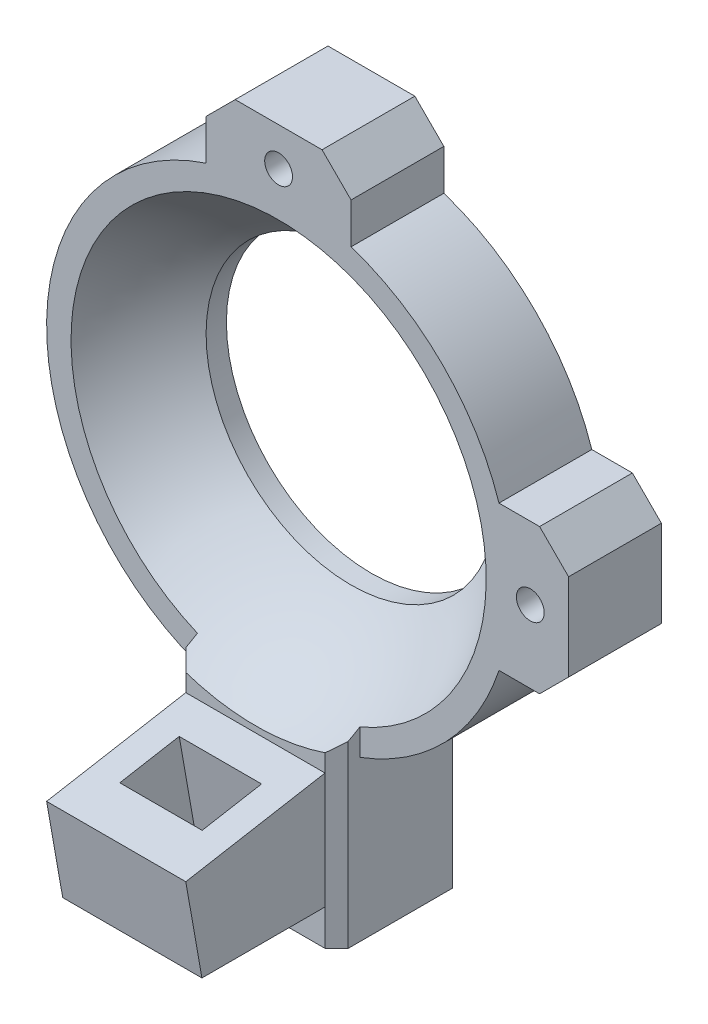
SolidWorks part; units mm, degrees
material "ABS"
ref_plane "Front Plane" through (0, 0, 0) normal (0, 0, 1) x (1, 0, 0)
ref_plane "Top Plane" through (0, 0, 0) normal (0, 1, 0) x (1, 0, 0)
ref_plane "Right Plane" through (0, 0, 0) normal (1, 0, 0) x (0, 0, -1)
sketch "Sketch1" plane through (0, 0, 0) normal (0, 0, 1) x (1, 0, 0)
  line L1 (-6.245, 21) -> (6.245, 21)
  line L2 (-6.245, 21) -> (-6.245, 19)
  line L3 (21, 6.245) -> (19, 6.245)
  line L4 (6.245, 21) -> (6.245, 19)
  line L5 (-6.245, 21) -> (6.245, 19) construction
  line L6 (-6.245, 19) -> (6.245, 21) construction
  line L7 (21, 6.245) -> (21, -6.245)
  line L8 (21, -6.245) -> (19, -6.245)
  line L10 (21, 6.245) -> (19, -6.245) construction
  line L11 (21, -6.245) -> (19, 6.245) construction
  circle A0 centre (0, 0) radius 12.5
  arc A1 (-6.245, 19) -> (0, -20) centre (0, 0) ccw
  arc A2 (19, 6.245) -> (6.245, 19) centre (0, 0) ccw
  arc A3 (0, -20) -> (19, -6.245) centre (0, 0) ccw
  point P3 (20, 0)
  point P4 (0, 20)
  point P13 (0, -20)
  dimension "D1" = 40
  dimension "D2" = 25
  dimension "D3" = 1
  dimension "D4" = 1
extrude "Boss-Extrude1" add sketch "Sketch1" along normal blind 8
ref_axis "Axis1" through (0, 0, 8) along (0, 0, -1)
sketch "Sketch18" plane through (0, 0, 0) normal (0, 0, 1) x (1, 0, 0)
  line L0 (-17, -10.5357) -> (-17, -19.7737)
  line L1 (-17, -19.7737) -> (-3, -19.7737)
  arc A0 (-6.245, 19) -> (19, -6.245) centre (0, 0) ccw construction
  arc A3 (-17, -10.5357) -> (-3, -19.7737) centre (0, 0) ccw
  point P5 (-10, -19.7737)
  dimension "D1" = 14
  dimension "D2" = 10
extrude "Boss-Extrude7" [suppressed] add sketch "Sketch18" along normal up to surface (8 mm away)
sketch "Sketch3" plane through (0, 0, 0) normal (0, 0, 1) x (1, 0, 0)
  line L0 (0, 0) -> (0, -32.5) construction
  line L1 (-7, -18.735) -> (-7, -32.5)
  line L2 (-7, -32.5) -> (7, -32.5)
  line L3 (7, -18.735) -> (7, -32.5)
  line L4 (-7, -18.735) -> (-7, -15.235)
  line L5 (-7, -15.235) -> (7, -15.235)
  line L6 (7, -15.235) -> (7, -18.735)
  circle A0 centre (0, 0) radius 20 construction
  dimension "D1" = 32.5
  dimension "D2" = 14
  dimension "D3" = 3.5
extrude "Boss-Extrude2" add sketch "Sketch3" along normal blind 10
sketch "Sketch2" plane through (0, 0, 0) normal (0, 1, 0) x (1, 0, 0)
  line L0 (0, -8) -> (0, 0) construction
  line L1 (0, -38.5) -> (0, 2.5)
  arc A0 (0, 2.5) -> (0, -38.5) centre (0, -18) ccw
  dimension "D1" = 41
  dimension "D2" = 18
revolve "Cut-Revolve2" cut sketch "Sketch2" angle 360 about axis through (0, 0, 8) along (0, 0, -1)
sketch "Sketch4" plane through (0, -32.5, 0) normal (0, -1, 0) x (1, 0, 0)
  line L0 (0, 10) -> (0, 0) construction
  line L8 (-7, 10) -> (7, 10) construction
  line L10 (-3.15, 8.15) -> (3.15, 8.15)
  line L11 (-3.15, 8.15) -> (-3.15, 1.85)
  line L12 (-3.15, 1.85) -> (3.15, 1.85)
  line L13 (3.15, 8.15) -> (3.15, 1.85)
  line L16 (-3.15, 8.15) -> (3.15, 1.85) construction
  line L17 (-3.15, 1.85) -> (3.15, 8.15) construction
  point P4 (0, 5)
  dimension "D1" = 6.3
extrude "Cut-Extrude1" cut sketch "Sketch4" against normal blind 12
sketch "Sketch11" plane through (0, 0, 0) normal (1, 0, 0) x (0, 0, -1)
  line L1 (-10, -19.4056) -> (-22, -21.5216)
  line L2 (-22, -21.5216) -> (-20.6098, -29.4056)
  line L3 (-20.6098, -29.4056) -> (-10, -29.4056)
  line L4 (-10, -29.4056) -> (-10, -19.4056)
  line L5 (-10, -32.5) -> (-10, -17.5285) construction
  line L6 (-8, -6.245) -> (-8, -18.735) construction
  circle A0 centre (-18, 0) radius 20.5 construction
  point P8 (-14.4402, -20.1886)
  dimension "D1" = 41
  dimension "D2" = 10
  dimension "D3" = 80
  dimension "D4" = 12
  dimension "D5" = 10
extrude "Boss-Extrude4" add sketch "Sketch11" along normal mid plane 12
sketch "Sketch12" plane through (0, 0, 0) normal (1, 0, 0) x (0, 0, -1)
  circle A0 centre (-20, 0) radius 20.5 construction
  dimension "D2" = 41
  dimension "D1" = 10
ref_point "Point1"
sketch "Sketch13" plane through (0, -17.1104, -3.017) normal (0, 0.9848, 0.1736) x (1, 0, 0)
  line L1 (-3.55, -16.2847) -> (3.55, -16.2847)
  line L2 (-3.55, -16.2847) -> (-3.55, -21.4847)
  line L3 (-3.55, -21.4847) -> (3.55, -21.4847)
  line L4 (3.55, -16.2847) -> (3.55, -21.4847)
  line L5 (-3.55, -16.2847) -> (3.55, -21.4847) construction
  line L6 (-3.55, -21.4847) -> (3.55, -16.2847) construction
  point P0 (0, -18.8847)
  dimension "D1" = 7.1
  dimension "D2" = 5.2
  dimension "D3" = 18.8847
extrude "Cut-Extrude5" cut sketch "Sketch13" against normal through all
sketch "Sketch22" plane through (0, 0, 0) normal (0, 0, 1) x (1, 0, 0)
  line L1 (-6.245, 21) -> (6.245, 21)
  line L2 (-6.245, 21) -> (-6.245, 25)
  line L3 (-6.245, 25) -> (6.245, 25)
  line L4 (6.245, 21) -> (6.245, 25)
  dimension "D1" = 4
extrude "Boss-Extrude10" add sketch "Sketch22" along normal up to surface (8 mm away) up to face at (5.7974, 3.6981, 8)
sketch "Sketch24" plane through (0, 0, 8) normal (0, 0, 1) x (1, 0, 0)
  line L0 (6.245, 25) -> (-6.245, 25) construction
  circle A0 centre (0, 21.7) radius 1.2
  point P2 (0, 20.5)
  point P6 (0, 25)
  dimension "D2" = 2.4
  dimension "D1" = 20.5
extrude "Cut-Extrude8" cut sketch "Sketch24" against normal offset from surface (6.5 mm away) 1.5 up to face at (5.7974, -1.1708, 0)
pattern_circular "CirPattern1" count 2 every 90 about axis through (0, 0, 0) along (0, 0, 1) of "Boss-Extrude10", "Cut-Extrude8"
chamfer "Chamfer1" distance 2.5 angle 45 4 edges at (25, -6.245, 4) (25, 6.245, 4) (6.245, 25, 4) (-6.245, 25, 4)
chamfer "Chamfer2" distance 1 angle 45 2 edges at (7, -25.0143, 10) (-7, -25.0143, 10)
